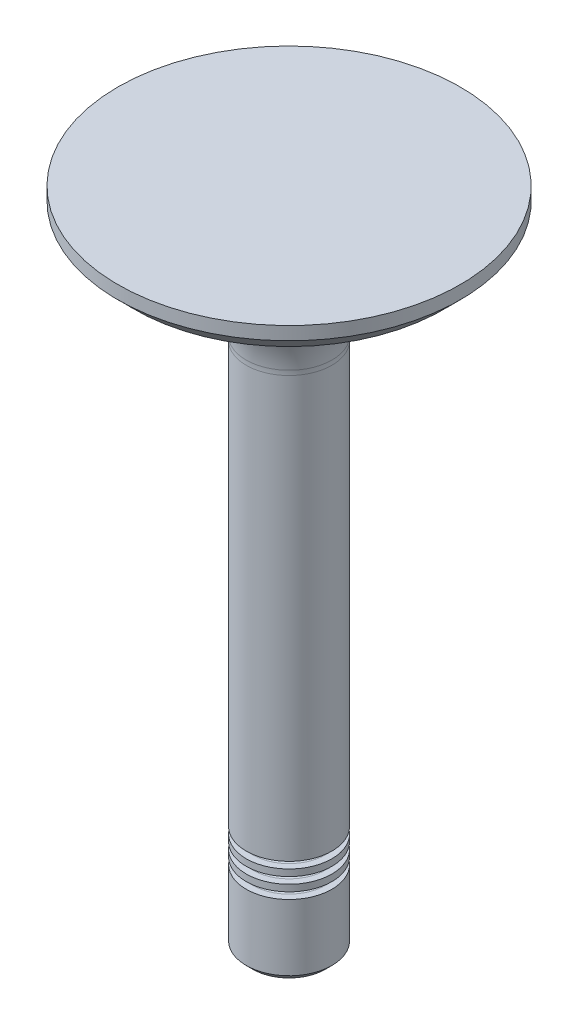
SolidWorks part; units mm, degrees
material "Silchrome I"
ref_plane "Front Plane" through (0, 0, 0) normal (0, 0, 1) x (1, 0, 0)
ref_plane "Top Plane" through (0, 0, 0) normal (0, 1, 0) x (1, 0, 0)
ref_plane "Right Plane" through (0, 0, 0) normal (1, 0, 0) x (0, 0, -1)
sketch "Sketch1" plane through (0, 0, 0) normal (0, 0, 1) x (1, 0, 0)
  line L0 (0, 224.083) -> (0, 124.083) construction
  line L1 (0, 224.083) -> (-25.92, 224.083)
  line L2 (-25.92, 224.083) -> (-25.92, 222.083)
  line L3 (-25.92, 222.083) -> (-23.328, 219.491)
  line L5 (-6.48, 204.053) -> (-6.48, 124.083)
  line L6 (-6.48, 124.083) -> (0, 124.083)
  line L7 (0, 224.083) -> (0, 124.083)
  arc A3 (-23.328, 219.491) -> (-6.48, 204.053) centre (-22.623, 203.348) cw
  dimension "D1" = 25.92
  dimension "D2" = 45
  dimension "D4" = 6.48
  dimension "D5" = 18.03
  dimension "D7" = 100
  dimension "D3" = 2.592
  dimension "D6" = 2
revolve "Revolve1" add sketch "Sketch1" angle 360 about L0
fillet "Fillet1" radius 10 1 edges at (-6.48, 204.053, 0)
chamfer "Chamfer1" distance 1 angle 45 1 edges at (-6.48, 124.083, 0)
sketch "Sketch5" plane through (0, 0, 0) normal (1, 0, 0) x (0, 0, -1)
  line L3 (-7.48, 138.083) -> (-5.48, 138.083)
  line L4 (0, 203.7831) -> (0, 125.083) construction
  line L5 (6.48, 203.7831) -> (-6.48, 203.7831) construction
  line L6 (6.48, 125.083) -> (-6.48, 125.083) construction
  line L7 (-7.48, 137.083) -> (-5.48, 137.083)
  line L8 (-7.48, 135.083) -> (-5.48, 135.083)
  line L9 (-7.48, 135.083) -> (-7.48, 136.083)
  line L10 (-7.48, 136.083) -> (-5.48, 136.083)
  line L12 (-7.48, 137.083) -> (-7.48, 138.083)
  line L13 (-7.48, 140.083) -> (-5.48, 140.083)
  line L14 (-7.48, 139.083) -> (-5.48, 139.083)
  line L15 (-7.48, 139.083) -> (-7.48, 140.083)
  arc A0 (-5.48, 135.083) -> (-5.48, 136.083) centre (-5.48, 135.583) ccw
  arc A1 (-5.48, 137.083) -> (-5.48, 138.083) centre (-5.48, 137.583) ccw
  arc A2 (-5.48, 139.083) -> (-5.48, 140.083) centre (-5.48, 139.583) ccw
  point P10 (-6.48, 135.583)
  dimension "D1" = 1
  dimension "D2" = 1
  dimension "D6" = 10
  dimension "D7" = 12
  dimension "D3" = 3
revolve "Cut-Revolve2" cut sketch "Sketch5" angle 360 about L4
equation "\"Valve Diameter\"= 51.84mm"
equation "\"Seat Angle Beta\"= 45deg"
equation "\"Seat Diameter\"= 46.656mm"
equation "\"Stem Diameter\"= 12.96mm"
equation "\"Max Lift\"= 18.03mm"
equation "\"Seat Width\"= 2.592mm"
equation "\"D1@Sketch1\"=\"Valve Diameter\"/2"
equation "\"D2@Sketch1\"=\"Seat Angle Beta\""
equation "\"D5@Sketch1\"=\"Max Lift\""
equation "\"Head Thickness\"= 2mm"
equation "\"Overall Length\"= 100mm"
equation "\"D7@Sketch1\"=\"Overall Length\""
equation "\"D3@Sketch1\"=\"Seat Width\""
equation "\"D6@Sketch1\"=\"Head Thickness\""
